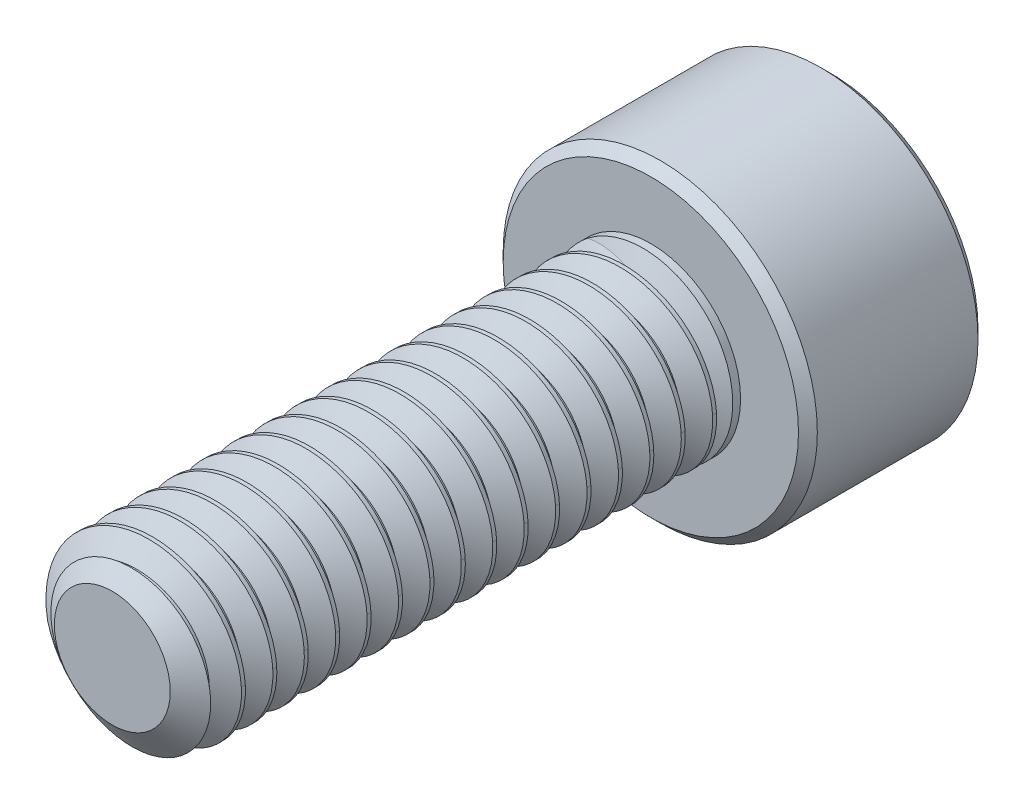
SolidWorks part; units mm, degrees
ref_plane "Front Plane" through (0, 0, 0) normal (0, 0, 1) x (1, 0, 0)
ref_plane "Top Plane" through (0, 0, 0) normal (0, 1, 0) x (1, 0, 0)
ref_plane "Right Plane" through (0, 0, 0) normal (1, 0, 0) x (0, 0, -1)
sketch "Sketch1" plane through (0, 0, 0) normal (0, 0, 1) x (1, 0, 0)
  circle A0 centre (0, 0) radius 2
  dimension "OD" = 4
extrude "Extrude1" add sketch "Sketch1" against normal blind 12
sketch "Sketch2" plane through (0, 0, 0) normal (0, 0, 1) x (1, 0, 0)
  circle A0 centre (0, 0) radius 2 construction
  circle A1 centre (0, 0) radius 2
curve "Helix/Spiral1" pitch 0.7 height 12.7 radius 2 centre (0, 0, 0) axis (0, 0, -1) start towards (0, 1, 0) parameters "pitch"=0.7
sketch "Sketch3" plane through (0, 0, 0) normal (1, 0, 0) x (0, 0, -1)
  line L0 (-0.6125, 2) -> (-0.35, 1.5453)
  line L1 (-0.35, 1.5453) -> (-0.2625, 1.5453)
  line L2 (-0.2625, 1.5453) -> (0, 2)
  line L3 (-0.6125, 2) -> (0, 2)
  line L4 (-0.3063, 2) -> (-0.3063, 1.5453) construction
  line L5 (-0.4813, 1.7727) -> (-0.1313, 1.7727) construction
  line L6 (0, 2) -> (0, -2) construction
  line L7 (0, -2) -> (12, -2) construction
  point P11 (3.15, -2)
  dimension "D1" = 0.0875
  dimension "D2" = 0.35
  dimension "D3" = 60
  dimension "D4" = 3.15
sweep "Cut-Sweep1" cut profiles "Sketch3" path "Helix/Spiral1"
sketch "Sketch4" plane through (0, 0, 0) normal (1, 0, 0) x (0, 0, -1)
  line L0 (0.4962, 2) -> (0, 1.2913)
  line L1 (0, 1.2913) -> (0, 2)
  line L2 (0.4962, 2) -> (0, 2)
  line L3 (-0.6125, 2) -> (0, 2) construction
  line L4 (0, 0) -> (7.0209, 0) construction
  dimension "D1" = 55
  dimension "D2" = 0.254
revolve "Cut-Revolve1" cut sketch "Sketch4" angle 360 about L4
sketch "Sketch5" plane through (0, 0, 0) normal (1, 0, 0) x (0, 0, -1)
  line L0 (12, -0.9741) -> (12, 1.9864) construction
  line L1 (12, 2) -> (0.1203, 2)
  line L2 (12, 2) -> (12, 0)
  line L3 (12, 0) -> (0.0001, 0)
  line L4 (0.0001, 1.6698) -> (0.0001, 0)
  line L5 (0.1203, 2) -> (0.0001, 1.6698)
  line L6 (0, 0) -> (9.9695, 0) construction
  point P3 (0.0001, 2)
  point P10 (0.0001, 2)
  dimension "D1" = 0.3302
  dimension "Thread min" = 0.0001
  dimension "D3" = 20
revolve "partially thread" [suppressed] add sketch "Sketch5" angle 360 about L6
sketch "Sketch6" plane through (0, 0, -12) normal (0, 0, -1) x (-1, 0, 0)
  circle A0 centre (0, 0) radius 3.5
  dimension "head dia" = 7
extrude "Extrude2" add sketch "Sketch6" along normal blind 4
sketch "Sketch7" plane through (0, 0, -16) normal (0, 0, -1) x (-1, 0, 0)
  line L1 (0, 1.7321) -> (-1.5, 0.866)
  line L2 (-1.5, 0.866) -> (-1.5, -0.866)
  line L3 (-1.5, -0.866) -> (0, -1.7321)
  line L4 (0, -1.7321) -> (1.5, -0.866)
  line L5 (1.5, -0.866) -> (1.5, 0.866)
  line L6 (1.5, 0.866) -> (0, 1.7321)
  circle A0 centre (0, 0) radius 1.5 construction
  dimension "hex dia" = 3
extrude "Cut-Extrude1" cut sketch "Sketch7" against normal blind 2.25
sketch "Sketch8" plane through (0, 0, -16) normal (0, 0, -1) x (-1, 0, 0)
  circle A0 centre (0, 0) radius 1.7321
extrude "Cut-Extrude2" cut sketch "Sketch8" against normal through all draft 45
chamfer "Chamfer1" distance 0.21 angle 45 2 edges at (-3.5, 0, -16) (-3.5, 0, -12)
sketch "Sketch9" plane through (0, 0, 0) normal (1, 0, 0) x (0, 0, -1)
  line L0 (0, 2) -> (0, -2) construction
  line L1 (3.85, 2) -> (3.85, -2) construction
  dimension "D1" = 3.85
sketch "Sketch10" plane through (0, 0, 0) normal (1, 0, 0) x (0, 0, -1)
  line L0 (12, 2) -> (12, 0)
  line L1 (12, 2) -> (11.825, 2)
  line L2 (11.825, 2) -> (10.9966, 0)
  line L3 (12, 0) -> (10.9966, 0)
  line L4 (12, 3.29) -> (12, -3.29) construction
  dimension "D1" = 22.5
  dimension "D2" = 0.175
revolve "Revolve1" add sketch "Sketch10" angle 360 about L3
equation "\"D3@Helix/Spiral1\" = \"screw length@Extrude1\"+\"pitch@Helix/Spiral1\""
equation "\"D1@Sketch3\" = \"pitch@Helix/Spiral1\"*.125"
equation "\"D2@Sketch3\" = \"pitch@Helix/Spiral1\"*.5"
equation "\"D1@Cut-Extrude1\" = \"hex dia@Sketch7\"*.75"
equation "\"D1@Chamfer1\" = \"head dia@Sketch6\"*.03"
equation "\"D1@Sketch9\" = \"pitch@Helix/Spiral1\"*5.5"
equation "\"D2@Sketch10\" = \"pitch@Helix/Spiral1\"*.25"
equation "\"D4@Sketch3\" = \"pitch@Helix/Spiral1\"*4.50"
